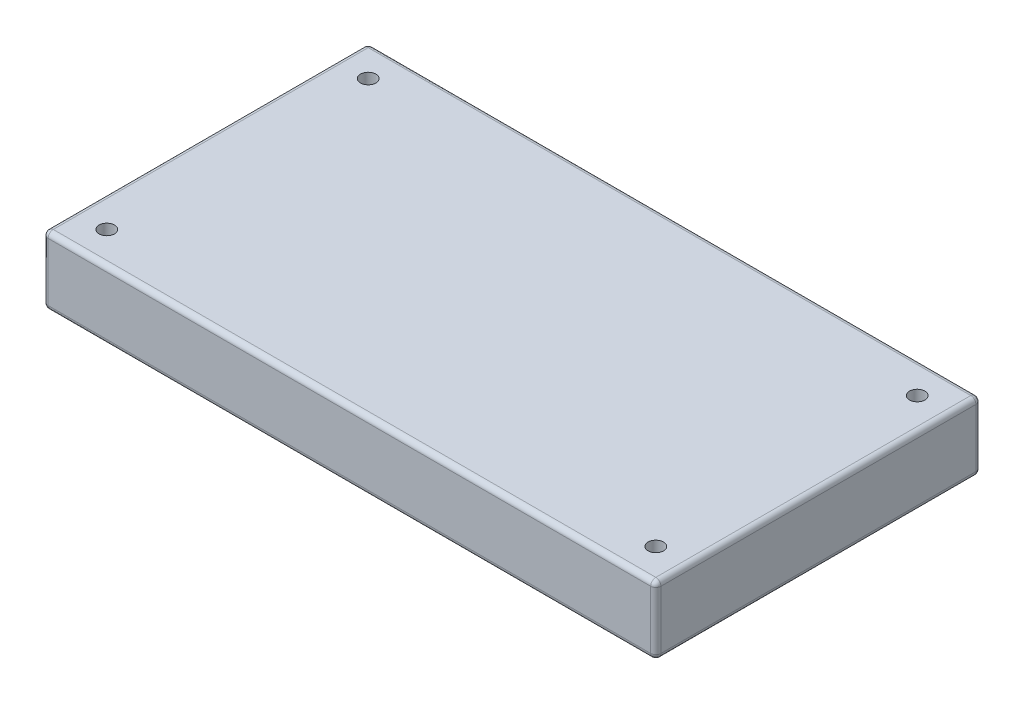
SolidWorks part; units mm, degrees
ref_plane "前视基准面" through (0, 0, 0) normal (0, 0, 1) x (1, 0, 0)
ref_plane "上视基准面" through (0, 0, 0) normal (0, 1, 0) x (1, 0, 0)
ref_plane "右视基准面" through (0, 0, 0) normal (1, 0, 0) x (0, 0, -1)
sketch "草图1" plane through (0, 0, 0) normal (0, 1, 0) x (1, 0, 0)
  line L1 (-59.55, 31.6) -> (59.55, 31.6)
  line L2 (-59.55, 31.6) -> (-59.55, -31.6)
  line L3 (-59.55, -31.6) -> (59.55, -31.6)
  line L4 (59.55, 31.6) -> (59.55, -31.6)
  line L5 (-59.55, 31.6) -> (59.55, -31.6) construction
  line L6 (-59.55, -31.6) -> (59.55, 31.6) construction
  line L7 (-59.55, 31.6) -> (59.55, 31.6) construction
  line L8 (-59.55, 31.6) -> (-59.55, -31.6) construction
  line L9 (-59.55, -31.6) -> (59.55, -31.6) construction
  line L10 (59.55, 31.6) -> (59.55, -31.6) construction
  line L11 (0, -31.6) -> (0, 31.6) construction
  line L12 (-59.55, 0) -> (59.55, 0) construction
  point P0 (0, 0)
  point P6 (0, 0)
  dimension "D1" = 119.1
  dimension "D2" = 63.2
extrude "凸台-拉伸1" add sketch "草图1" along normal blind 13.3 contours L2 L3 L4 L1
sketch "草图2" plane through (0, 13.3, 0) normal (0, 1, 0) x (1, 0, 0)
  circle A0 centre (-53.35, 25.4) radius 1.5
extrude "切除-拉伸1" cut sketch "草图2" against normal blind 13.3
sketch "草图3" plane through (0, 13.3, 0) normal (0, 1, 0) x (1, 0, 0)
  circle A0 centre (53.35, 25.4) radius 1.5
extrude "切除-拉伸2" cut sketch "草图3" against normal blind 13.3
sketch "草图4" plane through (0, 13.3, 0) normal (0, 1, 0) x (1, 0, 0)
  circle A0 centre (-53.35, -25.4) radius 1.5
extrude "切除-拉伸3" cut sketch "草图4" against normal blind 13.3
sketch "草图5" plane through (0, 13.3, 0) normal (0, 1, 0) x (1, 0, 0)
  circle A0 centre (53.35, -25.4) radius 1.5
extrude "切除-拉伸4" cut sketch "草图5" against normal blind 13.3
sketch "草图7" plane through (0, 0, 0) normal (0, 1, 0) x (1, 0, 0)
  circle A0 centre (-53.35, 20) radius 0.25
  point P2 (0, 0)
extrude "凸台-拉伸4" add sketch "草图7" along normal mid plane 5.3 contours A0
sketch "草图8" plane through (0, 0, 0) normal (0, 1, 0) x (1, 0, 0)
  circle A0 centre (-53.35, 18) radius 0.25
  circle A1 centre (-53.35, 16) radius 0.25
  circle A2 centre (-53.35, 14) radius 0.25
  circle A3 centre (-53.35, 12) radius 0.25
extrude "凸台-拉伸5" add sketch "草图8" along normal mid plane 5.3
sketch "草图9" plane through (0, 0, 0) normal (0, 1, 0) x (1, 0, 0)
  circle A2 centre (-55.35, 20) radius 0.25
  circle A3 centre (-55.35, 18) radius 0.25
  circle A4 centre (-55.35, 16) radius 0.25
  circle A5 centre (-55.35, 14) radius 0.25
  circle A6 centre (-55.35, 12) radius 0.25
extrude "凸台-拉伸6" add sketch "草图9" along normal mid plane 5.3
sketch "草图10" plane through (0, 0, 0) normal (0, 1, 0) x (1, 0, 0)
  circle A0 centre (-53.35, 8.2) radius 1
  circle A1 centre (-53.35, 3.1) radius 1
  circle A2 centre (-53.35, -14) radius 1
  circle A3 centre (-53.35, -19.1) radius 1
  circle A4 centre (53.35, 2.5) radius 1
  circle A5 centre (53.35, 12.7) radius 1
  circle A6 centre (53.35, -7.6) radius 0.5
  circle A7 centre (53.35, -11.5) radius 0.5
extrude "凸台-拉伸7" add sketch "草图10" along normal mid plane 5.3
fillet "圆角1" radius 1 7 edges at (-59.55, 13.3, 0) (-59.55, 6.65, 31.6) (-59.55, 0, 0) (59.55, 6.65, -31.6) (0, 13.3, -31.6) (-59.55, 6.65, -31.6) (0, 0, -31.6)
fillet "圆角2" radius 1 9 edges at (59.2571, 13.0071, -31.3071) (59.2571, 0.2929, -31.3071) (-59.2571, 0.2929, 31.3071) (-59.2571, 13.0071, 31.3071) (59.55, 13.3, 0.5) (59.55, 0, 0.5) (59.55, 6.65, 31.6) (0.5, 0, 31.6) (0.5, 13.3, 31.6)
